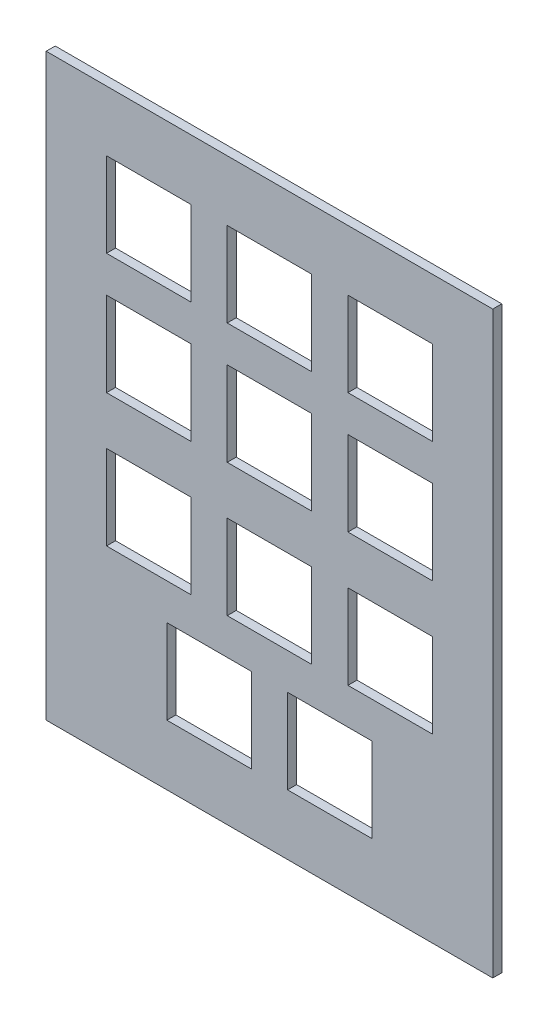
SolidWorks part; units mm, degrees
material "ABS"
ref_plane "Front Plane" through (0, 0, 0) normal (0, 0, 1) x (1, 0, 0)
ref_plane "Top Plane" through (0, 0, 0) normal (0, 1, 0) x (1, 0, 0)
ref_plane "Right Plane" through (0, 0, 0) normal (1, 0, 0) x (0, 0, -1)
sketch "Sketch1" plane through (0, 0, 0) normal (0, 0, 1) x (1, 0, 0)
  line L0 (-50, 30) -> (-44, 30) construction
  line L1 (0, 0) -> (-74, 0)
  line L2 (0, 0) -> (0, 96)
  line L3 (0, 96) -> (-74, 96)
  line L4 (-74, 0) -> (-74, 96)
  line L5 (-10, 44) -> (-24, 44)
  line L6 (-10, 72) -> (-24, 72)
  line L7 (-10, 72) -> (-10, 86)
  line L8 (-10, 86) -> (-24, 86)
  line L9 (-24, 72) -> (-24, 86)
  line L10 (-10, 44) -> (-10, 30)
  line L11 (-10, 30) -> (-24, 30)
  line L13 (-30, 86) -> (-44, 86)
  line L14 (-30, 86) -> (-30, 72)
  line L15 (-30, 72) -> (-44, 72)
  line L16 (-44, 86) -> (-44, 72)
  line L17 (-50, 86) -> (-64, 86)
  line L18 (-50, 86) -> (-50, 72)
  line L19 (-50, 72) -> (-64, 72)
  line L20 (-64, 86) -> (-64, 72)
  line L25 (-50, 72) -> (-44, 72) construction
  line L26 (-30, 72) -> (-24, 72) construction
  line L27 (-10, 52) -> (-24, 52)
  line L28 (-10, 52) -> (-10, 66)
  line L29 (-10, 66) -> (-24, 66)
  line L30 (-24, 52) -> (-24, 66)
  line L32 (-30, 66) -> (-44, 66)
  line L33 (-30, 66) -> (-30, 52)
  line L34 (-30, 52) -> (-44, 52)
  line L35 (-44, 66) -> (-44, 52)
  line L36 (-50, 66) -> (-64, 66)
  line L37 (-50, 66) -> (-50, 52)
  line L38 (-50, 52) -> (-64, 52)
  line L39 (-64, 66) -> (-64, 52)
  line L44 (-50, 52) -> (-44, 52) construction
  line L45 (-30, 52) -> (-24, 52) construction
  line L46 (-24, 44) -> (-24, 30)
  line L47 (-30, 44) -> (-44, 44)
  line L48 (-30, 44) -> (-30, 30)
  line L49 (-30, 30) -> (-44, 30)
  line L50 (-44, 44) -> (-44, 30)
  line L51 (-50, 44) -> (-64, 44)
  line L52 (-50, 44) -> (-50, 30)
  line L53 (-50, 30) -> (-64, 30)
  line L54 (-64, 44) -> (-64, 30)
  line L55 (-30, 30) -> (-24, 30) construction
  line L56 (-10, 72) -> (-10, 66) construction
  line L57 (-24, 52) -> (-24, 44) construction
  line L58 (-20, 24) -> (-34, 24)
  line L69 (-20, 24) -> (-20, 10)
  line L70 (-20, 10) -> (-34, 10)
  line L71 (-34, 24) -> (-34, 10)
  line L72 (-40, 24) -> (-54, 24)
  line L73 (-40, 24) -> (-40, 10)
  line L74 (-40, 10) -> (-54, 10)
  line L75 (-54, 24) -> (-54, 10)
  line L76 (-27, 30) -> (-27, 24) construction
  line L77 (-34, 17) -> (-40, 17) construction
  point P52 (0, 48)
  dimension "D3" = 14
  dimension "D4" = 6
  dimension "D5" = 14
  dimension "D7" = 8
  dimension "D2" = 10
  dimension "D1" = 10
  dimension "D10" = 10
  dimension "D6" = 10
extrude "Boss-Extrude1" add sketch "Sketch1" along normal blind 1.5
equation "\"D6@Sketch1\"=\"D10@Sketch1\""
equation "\"D2@Sketch1\"=\"D10@Sketch1\""
equation "\"D1@Sketch1\"=\"D10@Sketch1\""
